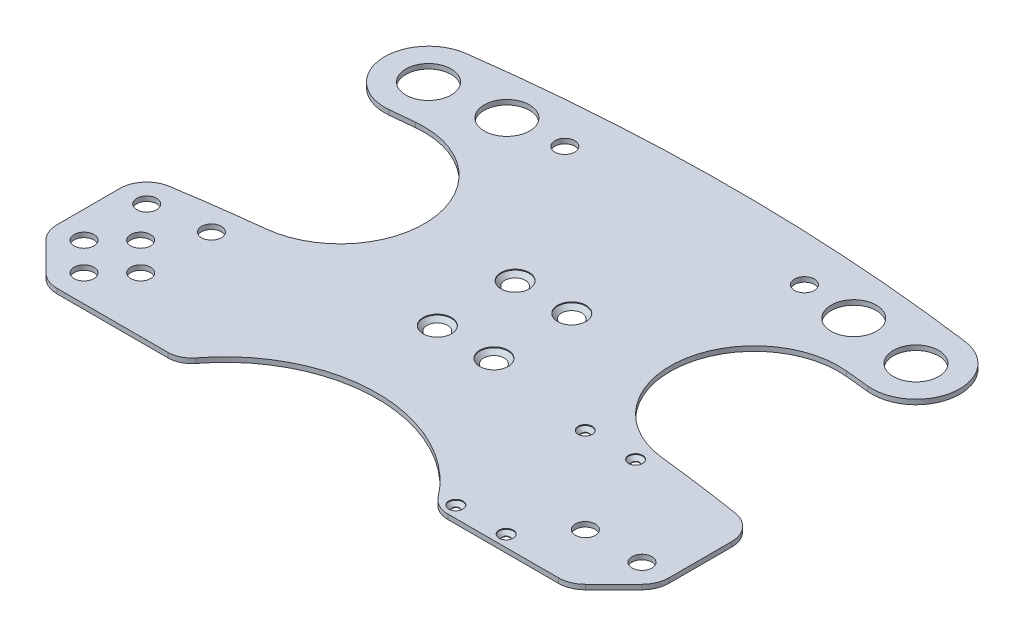
SolidWorks part; units mm, degrees
ref_plane "Front Plane" through (0, 0, 0) normal (0, 0, 1) x (1, 0, 0)
ref_plane "Top Plane" through (0, 0, 0) normal (0, 1, 0) x (1, 0, 0)
ref_plane "Right Plane" through (0, 0, 0) normal (1, 0, 0) x (0, 0, -1)
sketch "Sketch1" plane through (0, 0, 0) normal (0, 1, 0) x (1, 0, 0)
  line L1 (-120, -95) -> (120, -95)
  line L2 (-120, -95) -> (-120, 95)
  line L3 (-120, 95) -> (120, 95)
  line L4 (120, -95) -> (120, 95)
  line L5 (-120, -95) -> (120, 95) construction
  line L6 (-120, 95) -> (120, -95) construction
  line L7 (-10, 13.75) -> (10, 13.75)
  line L8 (-10, 13.75) -> (-10, -13.75)
  line L9 (-10, -13.75) -> (10, -13.75)
  line L10 (10, 13.75) -> (10, -13.75)
  line L11 (-10, 13.75) -> (10, -13.75) construction
  line L12 (-10, -13.75) -> (10, 13.75) construction
  circle A0 centre (0, 0) radius 95
  circle A1 centre (-10, 13.75) radius 2.5
  circle A2 centre (10, 13.75) radius 2.5
  circle A3 centre (10, -13.75) radius 2.5
  circle A4 centre (-10, -13.75) radius 2.5
  circle A5 centre (0, 0) radius 120
  dimension "D3" = 5
  dimension "D1" = 240
  dimension "D2" = 190
  dimension "D4" = 27.5
  dimension "D5" = 20
extrude "Boss-Extrude1" add sketch "Sketch1" along normal blind 1.7 contours A0 A4 L8 A1 L7 A2 L10 A3 L9 | A4 L9 A3 L10 A2 L7 A1 L8 | L3 A5 L1 A0 | L1 A5 L3 A0 region at (-105.6812, 0, 51.9346) region at (68.7642, 0, 68.7642) region at (-92.313, 0, 0) region at (0, 0, 0)
sketch "Sketch2" plane through (0, 1.7, 0) normal (0, 1, 0) x (1, 0, 0)
  line L0 (-81.1673, -40) -> (21.9115, -40) construction
  line L1 (-127.3056, -60) -> (138.909, -60) construction
  line L2 (-88.5406, 28.139) -> (-88.5406, -89.0376) construction
  line L3 (-88.5406, -40) -> (-88.5406, -60) construction
  line L4 (0, 21.6044) -> (0, -21.4213) construction
  line L5 (88.5406, 33.139) -> (88.5406, -84.0376) construction
  line L6 (-151.9803, -25) -> (55.006, -25) construction
  line L7 (-48.8837, 35) -> (62.426, 35) construction
  circle A0 centre (0, 0) radius 35
  circle A1 centre (0, 35) radius 2.5
  circle A2 centre (30.3109, 17.5) radius 2.5
  circle A3 centre (30.3109, -17.5) radius 2.5
  circle A4 centre (0, -35) radius 2.5
  circle A5 centre (-30.3109, -17.5) radius 2.5
  circle A6 centre (-30.3109, 17.5) radius 2.5
  circle A7 centre (-88.5406, -40) radius 3.5
  circle A8 centre (-88.5406, -50) radius 10
  circle A9 centre (-78.5406, -50) radius 3.5
  circle A10 centre (-88.5406, -60) radius 3.5
  circle A11 centre (-98.5406, -50) radius 3.5
  circle A12 centre (78.5406, -50) radius 3.5
  circle A13 centre (98.5406, -50) radius 3.5
  circle A14 centre (-98.5406, -27.8625) radius 3.5
  circle A15 centre (-78.5406, -25) radius 3.5
  circle A16 centre (0, 0) radius 45
  circle A17 centre (0, -580) radius 625
  circle A18 centre (0, -580) radius 645
  circle A19 centre (-86.0945, 59.2282) radius 8
  circle A20 centre (-61.2596, 62.0843) radius 8
  circle A21 centre (-86.0945, 59.2282) radius 15.5
  arc A22 (-73.3144, 95) -> (-73.3144, -95) centre (0, 0) ccw construction
  circle A23 centre (-61.2596, 62.0843) radius 9.5
  circle A24 centre (-86.0945, 59.2282) radius 9.5
  circle A25 centre (61.2596, 62.0843) radius 8
  circle A26 centre (86.0945, 59.2282) radius 8
  circle A27 centre (-42.3209, 63.6101) radius 3.5
  circle A28 centre (0, 0) radius 70
  circle A29 centre (42.3209, 63.6101) radius 3.5
  circle A30 centre (-98.5406, -50) radius 9.5
  circle A31 centre (42.3209, 63.6101) radius 9.5
  circle A32 centre (61.2596, 62.0843) radius 9.5
  circle A33 centre (0, -645.0455) radius 625
  point P17 (0, 0)
  point P21 (-88.5406, -50)
  point P37 (-88.5406, -50)
  point P56 (0, 65)
  point P57 (0, 45)
  point P68 (-76.6704, 60.4269)
  point P69 (-70.7097, 61.1124)
  point P81 (0, 0)
  dimension "D1" = 70
  dimension "D2" = 5
  dimension "D4" = 7
  dimension "D9" = 90
  dimension "D10" = 1250
  dimension "D11" = 20
  dimension "D12" = 16
  dimension "D14" = 6
  dimension "D13" = 19
  dimension "D17" = 140
  dimension "D18" = 6
  dimension "D5" = 20
  dimension "D6" = 40
  dimension "D8" = 15
  dimension "D15" = 6
  dimension "D3" = 6
  dimension "D7" = 4
extrude "Cut-Extrude1" cut sketch "Sketch2" against normal up to next contours A7 | A9 | A10 | A11 | A12 | A13 | A14 | A15 | A19 | A20 | A25 | A26 | A27 | A29
sketch "Sketch3" plane through (0, 1.7, 0) normal (0, 1, 0) x (1, 0, 0)
  line L1 (-84.5506, 43.8053) -> (-40.7771, 48.1872)
  line L2 (0, 100.6986) -> (0, -98.8678) construction
  line L3 (-10.3445, 0) -> (20.4144, 0) construction
  line L5 (84.5506, 43.8053) -> (40.7771, 48.1872)
  line L6 (-42.3209, 63.6101) -> (0, 0) construction
  line L7 (-36.306, 26.5871) -> (-55.2257, 55.0243)
  line L8 (-10.4964, 43.7587) -> (-29.4161, 72.1959)
  line L9 (10.4964, 43.7587) -> (29.4161, 72.1959)
  line L10 (36.306, 26.5871) -> (55.2257, 55.0243)
  line L11 (-108.0406, -50) -> (-108.0406, -27.8625)
  line L13 (-73.3144, -95) -> (73.3144, -95)
  line L14 (73.3144, 95) -> (-73.3144, 95)
  line L15 (-73.3144, -95) -> (73.3144, -95)
  line L16 (73.3144, 95) -> (-73.3144, 95)
  line L17 (-69.0406, -25) -> (-69.0406, -50)
  line L18 (-71.8231, -56.7175) -> (-81.8231, -66.7175)
  line L19 (-105.2581, -56.7175) -> (-95.2581, -66.7175)
  line L20 (-42.3209, 79.1101) -> (42.3209, 79.1101)
  line L21 (-78.5406, -15.5) -> (-42.2463, -15.5)
  line L22 (0, -45) -> (111.243, -45) construction
  line L23 (-88.5406, -69.5) -> (88.5406, -69.5)
  line L24 (69.0406, -15.5) -> (45.0406, -15.5)
  line L25 (78.5406, -15.5) -> (42.2463, -15.5)
  line L27 (108.0406, -50) -> (108.0406, -27.8625)
  line L28 (105.2581, -56.7175) -> (95.2581, -66.7175)
  line L29 (69.0406, -15.5) -> (69.0406, -69.5)
  line L30 (69.0406, -69.5) -> (45.0406, -69.5)
  line L31 (45.0406, -15.5) -> (45.0406, -69.5)
  line L32 (57.0406, -15.5) -> (57.0406, -69.5) construction
  line L33 (45.0406, -42.5) -> (69.0406, -42.5) construction
  circle A0 centre (-86.0945, 59.2282) radius 15.5
  arc A1 (-73.3144, 95) -> (-73.3144, -95) centre (0, 0) ccw construction
  circle A2 centre (-42.3209, 63.6101) radius 15.5
  circle A3 centre (86.0945, 59.2282) radius 15.5
  circle A4 centre (42.3209, 63.6101) radius 15.5
  circle A5 centre (0, 0) radius 45
  circle A6 centre (-98.5406, -27.8625) radius 9.5
  circle A7 centre (-98.5406, -27.8625) radius 3.5 construction
  arc A8 (-73.3144, 95) -> (-73.3144, -95) centre (0, 0) ccw
  arc A9 (73.3144, -95) -> (73.3144, 95) centre (0, 0) ccw
  arc A10 (-73.3144, 95) -> (-73.3144, -95) centre (0, 0) ccw
  arc A11 (73.3144, -95) -> (73.3144, 95) centre (0, 0) ccw
  circle A12 centre (-78.5406, -25) radius 9.5
  circle A13 centre (-88.5406, -60) radius 9.5
  circle A14 centre (-98.5406, -50) radius 9.5
  circle A15 centre (-78.5406, -50) radius 9.5
  circle A17 centre (98.5406, -50) radius 9.5
  circle A18 centre (78.5406, -50) radius 9.5
  arc A19 (73.3144, -95) -> (73.3144, 95) centre (0, 0) ccw construction
  arc A20 (-45.0406, -69.5) -> (45.0406, -69.5) centre (0, -98.6511) cw
  circle A21 centre (98.5406, -27.8625) radius 9.5
  circle A22 centre (98.5406, -50) radius 9.5
  circle A23 centre (88.5406, -60) radius 9.5
  circle A24 centre (-73.1485, 15.1063) radius 29.692
  circle A25 centre (73.1485, 15.1063) radius 29.692
  circle A26 centre (48.1506, -19.64) radius 1.3
  circle A27 centre (65.9306, -19.64) radius 1.3
  circle A28 centre (65.9306, -65.36) radius 1.3
  circle A29 centre (48.1506, -65.36) radius 1.3
  circle A30 centre (0, -580) radius 645
  circle A31 centre (0, -580) radius 660.5
  circle A32 centre (0, -645.0455) radius 634.5
  arc M45 (-73.3144, 95) -> (-73.3144, -95) centre (0, 0) ccw
  line M46 (-73.3144, -95) -> (73.3144, -95)
  arc M47 (73.3144, -95) -> (73.3144, 95) centre (0, 0) ccw
  line M48 (73.3144, 95) -> (-73.3144, 95)
  dimension "D1" = 90
  dimension "D3" = 6
  dimension "D5" = 2.6
  dimension "D4" = 24
  dimension "D6" = 17.78
  dimension "D7" = 45.72
  dimension "D2" = 0
extrude "Cut-Extrude2" cut sketch "Sketch3" against normal up to next contours A24 L1 A0 A14 L11 A6 L21 M45 | A24 | L28 A23 L23 A13 L19 A14 A10 A17 M46 M47 | A20 L23 | L5 A25 L24 L25 A21 L27 A17 A11 A3 | A25 | A30 A0 M45 | A31 A11 M48 M45 | A0 A31 A10 | A31 A3 M47 | A30 A3 M47 | A6 A32 A14 L11 M45 | A11 A32 A21 L27 A17 | A26 | A27 | A28 | A29 region at (-105.8887, 1.7, -12.959) region at (-73.1485, 1.7, -15.1063) region at (-102.839, 1.7, -59.5932) region at (-94.2652, 1.7, -72.7135) region at (0, 1.7, -86.2332) region at (-111.2756, 1.7, 31.2797) region at (0, 1.7, 81.3426) region at (0, 1.7, 59.4787) region at (73.1485, 1.7, -15.1063) region at (105.8887, 1.7, -12.959) region at (111.2756, 1.7, 31.2797) region at (94.2652, 1.7, -72.7135) region at (102.839, 1.7, -59.5932)
hole_wizard "CSK for M5 Flat Head Machine Screw1" positions "Sketch4" profile "Sketch5" countersink size "M5" standard "ANSI Metric"
sketch "Sketch4" plane through (0, 1.7, 0) normal (0, 1, 0) x (1, 0, 0)
  point P0 (-10, 13.75)
  point P3 (10, 13.75)
  point P6 (10, -13.75)
  point P9 (-10, -13.75)
sketch "Sketch5" plane through (-10, 1.7, -13.75) normal (1, 0, 0) x (0, 0, 1)
  line L0 (0, 0) -> (0, 6.5022)
  line L1 (0, 6.5022) -> (2.5, 5)
  line L2 (2.5, 5) -> (2.5, 2.8)
  line L3 (2.5, 2.8) -> (5, 0.3)
  line L4 (5, 0.3) -> (5, 0)
  line L6 (5, 0) -> (0, 0)
  line L7 (-2.5, 2.8) -> (-5, 0.3) construction
  line L10 (0, 6.5022) -> (-2.5, 5) construction
  line L11 (0, -6.35) -> (0, 107.95) construction
  dimension "Hole Dia." = 5
  dimension "Hole Depth" = 5
  dimension "C'Sink Dia." = 10
  dimension "C'Sink Angle" = 90
  dimension "Drill Angle" = 118
  dimension "Head Clearance" = 0.3
hole_wizard "CSK for M2.5 Flat Head Machine Screw1" positions "Sketch6" profile "Sketch7" countersink size "M2.5" standard "ANSI Metric"
sketch "Sketch6" plane through (0, 1.7, 0) normal (0, 1, 0) x (1, 0, 0)
  point P0 (48.1506, -19.64)
  point P3 (65.9306, -19.64)
  point P6 (65.9306, -65.36)
  point P9 (48.1506, -65.36)
sketch "Sketch7" plane through (48.1506, 1.7, 19.64) normal (1, 0, 0) x (0, 0, 1)
  line L0 (0, 0) -> (0, 5.7511)
  line L1 (0, 5.7511) -> (1.25, 5)
  line L2 (1.25, 5) -> (1.25, 1.55)
  line L3 (1.25, 1.55) -> (2.5, 0.3)
  line L4 (2.5, 0.3) -> (2.5, 0)
  line L6 (2.5, 0) -> (0, 0)
  line L7 (-1.25, 1.55) -> (-2.5, 0.3) construction
  line L10 (0, 5.7511) -> (-1.25, 5) construction
  line L11 (0, -6.35) -> (0, 107.95) construction
  dimension "Hole Dia." = 2.5
  dimension "Hole Depth" = 5
  dimension "C'Sink Dia." = 5
  dimension "C'Sink Angle" = 90
  dimension "Drill Angle" = 118
  dimension "Head Clearance" = 0.3
fillet "Fillet1" radius 8.5 2 edges at (45.0406, 0.85, 69.5) (-45.0406, 0.85, 69.5)
